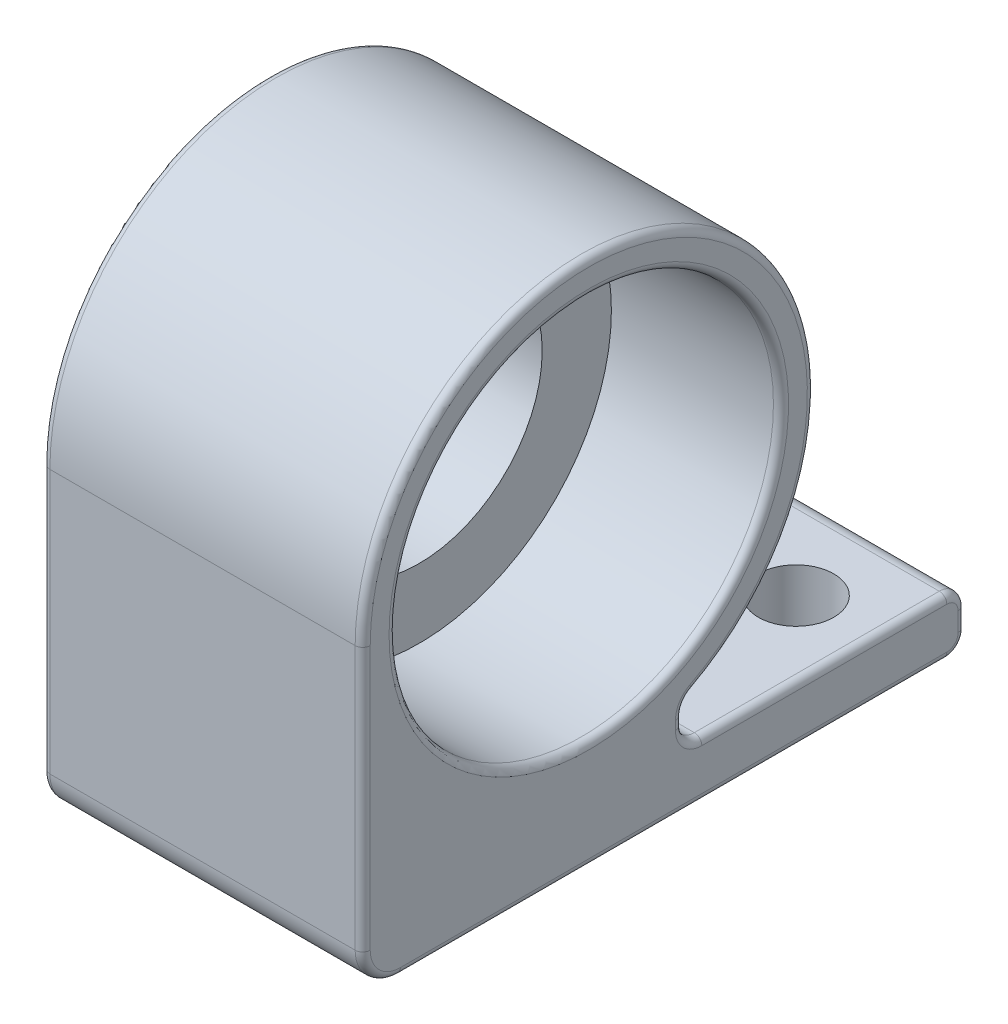
SolidWorks part; units mm, degrees
ref_plane "前视基准面" through (0, 0, 0) normal (0, 0, 1) x (1, 0, 0)
ref_plane "上视基准面" through (0, 0, 0) normal (0, 1, 0) x (1, 0, 0)
ref_plane "右视基准面" through (0, 0, 0) normal (1, 0, 0) x (0, 0, -1)
sketch "草图1" plane through (0, 0, 0) normal (1, 0, 0) x (0, 0, -1)
  line L0 (0, -8) -> (9.5, -8)
  line L1 (10, -7) -> (10, -7.5)
  line L2 (0, 0) -> (0, -12.2697) construction
  line L3 (0, -8) -> (-5, -8)
  line L4 (2.5, -5.7663) -> (2.5, -6)
  line L6 (9.5, -6.5) -> (3, -6.5)
  line L8 (-6, 0) -> (-6, -7)
  arc A0 (2.7692, -5.3227) -> (-6, 0) centre (0, 0) ccw
  arc A1 (10, -7.5) -> (9.5, -8) centre (9.5, -7.5) cw
  arc A2 (2.5, -6) -> (3, -6.5) centre (3, -6) ccw
  arc A3 (9.5, -6.5) -> (10, -7) centre (9.5, -7) cw
  arc A4 (-6, -7) -> (-5, -8) centre (-5, -7) ccw
  arc A5 (2.5, -5.7663) -> (2.7692, -5.3227) centre (3, -5.7663) cw
  point P14 (3.9686, -6.5)
  dimension "D1" = 0.5
  dimension "D2" = 1
extrude "凸台-拉伸1" add sketch "草图1" along normal blind 8.5
sketch "草图2" plane through (0, 0, 0) normal (-1, 0, 0) x (0, 0, 1)
  circle A0 centre (0, 0) radius 2
extrude "切除-拉伸1" cut sketch "草图2" against normal blind 10
sketch "草图6" plane through (8.5, 0, 0) normal (1, 0, 0) x (0, 0, -1)
  circle A0 centre (0, 0) radius 5.1
extrude "切除-拉伸3" cut sketch "草图6" against normal blind 4.5
hole_wizard "5/16-18 螺纹孔1" positions "草图3" profile "草图4" tap size "5/16-18" standard "ANSI Inch"
sketch "草图3" plane through (4, 0, 0) normal (1, 0, 0) x (0, 0, -1)
  point P0 (0, 0)
sketch "草图4" plane through (4, 0, 0) normal (0, 1, 0) x (0, 0, -1)
  line L0 (0, 0) -> (0, 5.1611)
  line L1 (0, 5.1611) -> (3.2639, 3.2)
  line L2 (3.2639, 3.2) -> (3.2639, 0)
  line L5 (3.2639, 0) -> (0, 0)
  line L10 (0, 5.1611) -> (-3.2639, 3.2) construction
  line L11 (0, -6.35) -> (0, 107.95) construction
  dimension "螺纹孔钻头直径" = 6.5278
  dimension "螺纹孔钻头深度" = 3.2
  dimension "导头角度" = 118
cosmetic thread "孔螺蚊线1" parameters "D1"=3.2, "D2"=7.9375
sketch "草图5" plane through (0, -6.5, 0) normal (0, 1, 0) x (1, 0, 0)
  line L1 (0, 9.5) -> (0, 3) construction
  line L2 (8.5, 9.5) -> (8.5, 3) construction
  circle A0 centre (2, 7.5) radius 1
  circle A1 centre (6.5, 7.5) radius 1
  dimension "D1" = 2
  dimension "D2" = 2
extrude "切除-拉伸2" cut sketch "草图5" against normal up to next
fillet "圆角1" radius 0.2 24 edges at (0, 5.1291, -3.1132) (0, 0, 2) (8.5, 5.1291, -3.1132) (8.5, 0, -5.1) (0, -7.25, -10) (0, -6.6464, -9.8536) (0, -6.5, -6.25) (0, -6.3536, -2.6464) (0, -5.8831, -2.5) (0, -5.5068, -2.5726) (0, -3.5, 6) (0, -7.8536, -9.8536) (8.5, -3.5, 6) (8.5, -5.5068, -2.5726) (8.5, -5.8831, -2.5) (8.5, -6.3536, -2.6464) (8.5, -6.5, -6.25) (8.5, -6.6464, -9.8536) (8.5, -7.25, -10) (8.5, -7.8536, -9.8536) (0, -7.7071, 5.7071) (0, -8, -2.25) (8.5, -8, -2.25) (8.5, -7.7071, 5.7071)
